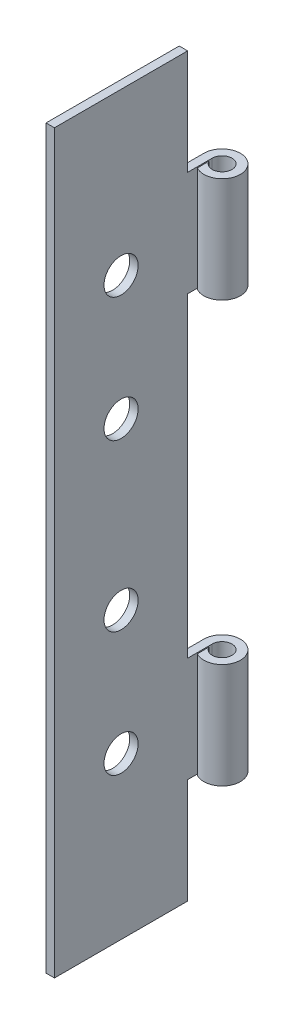
SolidWorks part; units mm, degrees
ref_plane "Front Plane" through (0, 0, 0) normal (0, 0, 1) x (1, 0, 0)
ref_plane "Top Plane" through (0, 0, 0) normal (0, 1, 0) x (1, 0, 0)
ref_plane "Right Plane" through (0, 0, 0) normal (1, 0, 0) x (0, 0, -1)
sketch "Sketch1" plane through (0, 0, 0) normal (1, 0, 0) x (0, 0, -1)
  line L0 (0, 0) -> (0, 88.9) construction
  line L1 (0, 0) -> (19.05, 0) construction
  line L2 (9.144, 12.7) -> (13.1064, 12.7) construction
  line L3 (0, 0) -> (-19.05, 0) construction
  point P3 (11.1252, 12.7)
  point P5 (11.1252, 76.2)
  point P6 (0, 12.7)
  point P9 (-101.6, 88.9)
  point P10 (11.1252, 12.7)
  point P11 (-25.4, 88.9)
  point P12 (-177.8, 88.9)
  point P13 (-11.1252, 76.2)
  point P14 (-11.1252, 12.7)
  dimension "Knuckle Length" = 12.7
  dimension "Length Corner" = 12.7
  dimension "Height Corner" = 7.9248
  dimension "Overall Width" = 38.1
  dimension "Leaf Height" = 88.9
  dimension "MTG Dia" = 3.9624
  dimension "Num Holes" = 101.6
  dimension "Spring Knuckles" = 25.4
  dimension "Num Knuckles" = 177.8
  dimension "D2" = 7.9248
  dimension "Length Corner 2" = 12.7
  dimension "D4" = 12.7
sketch "Sketch2" plane through (0, 0, 0) normal (0, 1, 0) x (1, 0, 0)
  line L0 (1.016, 0) -> (3.3973, 0) construction
  line L1 (0, 19.05) -> (1.016, 19.05) construction
  line L2 (-0.889, 16.1766) -> (0, 16.1766) construction
  line L3 (2.2066, 1.1906) -> (2.2066, 2.2066) construction
  line L5 (2.2066, 2.2066) -> (2.2066, 16.1766) construction
  circle A0 centre (2.2066, 0) radius 1.1906 construction
  point P9 (2.2066, 1.3176)
  point P10 (1.143, 16.1766)
  dimension "Leaf Thickness" = 1.016
  dimension "Pin Dia" = 2.3813
  dimension "Wire Dia" = 0.889
  dimension "Spring Leg Length" = 13.97
  dimension "Bend Clearence" = 0.127
  dimension "D1" = 0.889
  dimension "Open Close Offset" = 2.032
sketch "Sketch3" plane through (0, 0, 0) normal (0, 1, 0) x (1, 0, 0)
  line L0 (1.016, 19.05) -> (0, 19.05)
  line L1 (0, 19.05) -> (0, 0)
  line L2 (0, 0) -> (0, 19.05) construction
  line L3 (1.016, 19.05) -> (1.016, 0)
  line L4 (1.143, 1.9334) -> (1.143, 0.5351)
  arc A0 (0, 0) -> (1.143, 1.9334) centre (2.2066, 0) ccw
  arc A1 (1.016, 0) -> (1.143, 0.5351) centre (2.2066, 0) ccw
extrude "Boss-Extrude1" [suppressed] add sketch "Sketch3" along normal up to vertex
sketch "Sketch4" plane through (0, 0, 0) normal (0, 1, 0) x (1, 0, 0)
  line L0 (0, 0) -> (0, -19.05)
  line L1 (0, -19.05) -> (1.016, -19.05)
  line L2 (1.016, -19.05) -> (1.016, 0)
  line L3 (1.143, -0.5351) -> (1.143, -1.9334)
  line L4 (1.016, 0) -> (3.3973, 0) construction
  line L5 (0, 0) -> (0, 19.05) construction
  arc A0 (1.143, -1.9334) -> (0, 0) centre (2.2066, 0) ccw
  arc A1 (1.143, -0.5351) -> (1.016, 0) centre (2.2066, 0) ccw
extrude "Boss-Extrude2" add sketch "Sketch4" along normal up to vertex (88.9 mm away) separate body up to point (0, 88.9, 0)
sketch "Sketch7" plane through (0, 0, 0) normal (1, 0, 0) x (0, 0, -1)
  line L0 (-2.9686, 76.2) -> (2.9686, 76.2)
  line L1 (-2.9686, 25.4) -> (2.9686, 25.4)
  line L2 (-2.9686, 25.4) -> (-2.9686, 12.7)
  line L3 (-2.9686, 12.7) -> (2.9686, 12.7)
  line L4 (2.9686, 25.4) -> (2.9686, 12.7)
  line L5 (-2.9686, 50.8) -> (2.9686, 50.8)
  line L6 (-2.9686, 50.8) -> (-2.9686, 38.1)
  line L7 (2.9686, 50.8) -> (2.9686, 38.1)
  line L8 (-2.9686, 38.1) -> (2.9686, 38.1)
  line L9 (-2.9686, 25.4) -> (-2.9686, 50.8) construction
  line L10 (-2.9686, 76.2) -> (-2.9686, 63.5)
  line L11 (2.9686, 76.2) -> (2.9686, 63.5)
  line L12 (-2.9686, 63.5) -> (2.9686, 63.5)
  line L13 (-2.9686, 101.6) -> (2.9686, 101.6)
  line L14 (-2.9686, 101.6) -> (-2.9686, 88.9)
  line L15 (2.9686, 101.6) -> (2.9686, 88.9)
  line L16 (-2.9686, 88.9) -> (2.9686, 88.9)
  point P5 (0, 12.7)
  dimension "D2" = 5.9372
  dimension "D3" = 4
extrude "Cut-Extrude2" [suppressed] cut sketch "Sketch7" along normal through all
sketch "Sketch8" plane through (0, 0, 0) normal (1, 0, 0) x (0, 0, -1)
  line L0 (-2.9686, 12.7) -> (2.9686, 12.7) construction
  line L1 (-2.9686, 12.7) -> (2.9686, 12.7)
  line L2 (-2.9686, 12.7) -> (-2.9686, 0)
  line L3 (-2.9686, 0) -> (2.9686, 0)
  line L4 (2.9686, 12.7) -> (2.9686, 0)
  line L5 (-2.9686, 25.4) -> (-2.9686, 12.7) construction
  line L6 (-2.9686, 38.1) -> (2.9686, 38.1)
  line L7 (-2.9686, 38.1) -> (-2.9686, 25.4)
  line L8 (-2.9686, 25.4) -> (2.9686, 25.4)
  line L9 (2.9686, 38.1) -> (2.9686, 25.4)
  line L10 (-2.9686, 12.7) -> (-2.9686, 38.1) construction
  line L11 (-2.9686, 63.5) -> (2.9686, 63.5)
  line L12 (-2.9686, 63.5) -> (-2.9686, 50.8)
  line L13 (-2.9686, 50.8) -> (2.9686, 50.8)
  line L14 (2.9686, 63.5) -> (2.9686, 50.8)
  line L15 (-2.9686, 88.9) -> (2.9686, 88.9)
  line L16 (-2.9686, 88.9) -> (-2.9686, 76.2)
  line L17 (-2.9686, 76.2) -> (2.9686, 76.2)
  line L18 (2.9686, 88.9) -> (2.9686, 76.2)
extrude "Cut-Extrude3" cut sketch "Sketch8" along normal through all
sketch "Sketch10" plane through (0, 0, 0) normal (1, 0, 0) x (0, 0, -1)
  line L1 (2.9686, 50.8) -> (-2.9686, 50.8)
  line L2 (2.9686, 50.8) -> (2.9686, 38.1)
  line L3 (2.9686, 38.1) -> (-2.9686, 38.1)
  line L4 (-2.9686, 50.8) -> (-2.9686, 38.1)
  line L5 (-2.9686, 12.7) -> (2.9686, 12.7) construction
  line L7 (0, 0) -> (0, 88.9) construction
  point P4 (0, 38.1)
  dimension "D2" = 38.1
extrude "Cut-Extrude4" cut sketch "Sketch10" along normal through all
sketch "Sketch9" plane through (0, 0, 0) normal (0, 1, 0) x (1, 0, 0)
  line L0 (1.016, 0) -> (3.3973, 0) construction
  circle A0 centre (2.2066, 0) radius 1.1906
extrude "Boss-Extrude3" [suppressed] add sketch "Sketch9" along normal up to vertex separate body
ref_plane "Plane1" through (0, 38.5445, 0) normal (0, 1, 0) x (1, 0, 0)
sketch "Sketch11" plane through (0, 38.5445, 0) normal (0, 1, 0) x (1, 0, 0)
  circle A0 centre (2.2066, 0) radius 2.2066
curve "Helix/Spiral1" pitch 0.9449 height 11.811 turns 12.5
ref_plane "Plane2" through (0, 50.3555, 0) normal (0, 1, 0) x (1, 0, 0)
sketch "Sketch12" plane through (0, 38.5445, 0) normal (0, 1, 0) x (1, 0, 0)
  line L0 (0, 16.1766) -> (0, 3.3099)
  line L1 (2.2066, 2.2066) -> (1.1033, 2.2066)
  line L2 (-0.889, 16.1766) -> (0, 16.1766) construction
  line L3 (1.1033, 3.3099) -> (1.1033, 2.2066) construction
  arc A0 (1.1033, 2.2066) -> (0, 3.3099) centre (1.1033, 3.3099) cw
sketch "Sketch13" plane through (0, 50.3555, 0) normal (0, 1, 0) x (1, 0, 0)
  line L0 (0, -3.3099) -> (0, -16.1766)
  line L1 (0, 16.1766) -> (0, 3.3099) construction
  line L2 (1.1033, -2.2066) -> (2.2066, -2.2066)
  line L3 (2.2066, 2.2066) -> (1.1033, 2.2066) construction
  arc A0 (0, -3.3099) -> (1.1033, -2.2066) centre (1.1033, -3.3099) cw
  circle A2 centre (2.2066, 0) radius 2.2066 construction
curve "CompCurve1"
ref_plane "Plane3" through (0, 0, -16.1766) normal (0, 0, 1) x (1, 0, 0)
sketch "Sketch14" plane through (0, 0, -16.1766) normal (0, 0, 1) x (1, 0, 0)
  line L0 (-0.4445, 0) -> (-0.4445, 38.5445) construction
  line L1 (-0.889, 0) -> (0, 0) construction
  line L3 (4.4132, 38.5445) -> (0, 38.5445) construction
  circle A0 centre (-0.4445, 38.5445) radius 0.4445
  dimension "D1" = 0.889
sweep "Sweep1" [suppressed] add profiles "Sketch14" path "CompCurve1"
sketch "Sketch15" plane through (0, 0, 0) normal (1, 0, 0) x (0, 0, -1)
  line L0 (9.144, 12.7) -> (13.1064, 12.7) construction
  circle A0 centre (11.1252, 12.7) radius 1.9812
  circle A1 centre (-11.1252, 12.7) radius 1.9812
  dimension "D1" = 22.2504
extrude "Cut-Extrude5" [suppressed] cut sketch "Sketch15" along normal through all
ref_plane "Mid Plane" [suppressed] through (0, 44.45, 0) normal (0, -1, 0) x (-1, 0, 0)
mirror "Mirror1" [suppressed] about plane through (0, 44.45, 0) normal (0, -1, 0)
sketch "Sketch16" plane through (0, 0, 0) normal (-1, 0, 0) x (0, 0, 1)
  line L0 (-13.0076, 44.45) -> (44.3882, 44.45) construction
  line L1 (11.0093, 95.5293) -> (11.0093, -12.8397) construction
  line L2 (2.9686, 63.5) -> (2.9686, 25.4) construction
  line L3 (19.05, 88.9) -> (19.05, 0) construction
  line L4 (2.9686, 88.9) -> (19.05, 88.9) construction
  line L5 (2.9686, 0) -> (19.05, 0) construction
  circle A0 centre (11.0093, 54.45) radius 2.06
  circle A1 centre (11.0093, 69.45) radius 2.06
  circle A2 centre (11.0093, 34.45) radius 2.06
  circle A3 centre (11.0093, 19.45) radius 2.06
  point P18 (19.05, 58.2708)
  dimension "D3" = 4.12
  dimension "D2" = 10
  dimension "D1" = 2
extrude "Cut-Extrude6" cut sketch "Sketch16" against normal blind 2.54
equation "\"Num Knuckles\"=5"
equation "\"D1@Sketch7\"=\"Knuckle Length@Sketch1\""
equation "\"D2@Sketch7\" = ( 2 * \"Leaf Thickness@Sketch2\" ) + \"Pin Dia@Sketch2\" + ( .04 * \"Overall Width@Sketch1\" )"
equation "\"D4@Sketch7\"=\"Knuckle Length@Sketch1\"*2"
equation "\"D3@Sketch7\" = int ( \"Num Knuckles@Sketch1\" / 2 )  + 1"
equation "\"D2@Sketch8\"=\"D4@Sketch7\""
equation "\"D1@Sketch8\"=\"D3@Sketch7\""
equation "\"Spring Knuckles\"= 1"
equation "\"D1@Sketch10\"= \"Knuckle Length@Sketch1\" * \"Spring Knuckles@Sketch1\""
equation "\"D2@Sketch10\"=\"Knuckle Length@Sketch1\"*(\"Num Knuckles@Sketch1\"-\"Spring Knuckles@Sketch1\")/2"
equation "\"D1@Plane1\"=\"D2@Sketch10\"+(\"Wire Dia@Sketch2\"/2)"
equation "\"D3@Helix/Spiral1\"=(\"Spring Knuckles@Sketch1\"*\"Knuckle Length@Sketch1\")-\"Wire Dia@Sketch2\""
equation "\"D1@Plane2\"=\"D3@Helix/Spiral1\""
equation "\"D1@Sketch14\"=\"Wire Dia@Sketch2\""
equation "\"Num Holes\"=4"
equation "\"D1@Sketch1\"=\"Length Corner@Sketch1\""
equation "\"D1@Sketch2\"= \"Wire Dia@Sketch2\""
equation "\"Knuckle Length@Sketch1\"=\"Leaf Height@Sketch1\"/\"Num Knuckles@Sketch1\""
equation "\"D2@Sketch1\"=\"Height Corner@Sketch1\""
equation "\"D4@Sketch1\" = \"Length Corner 2@Sketch1\""
